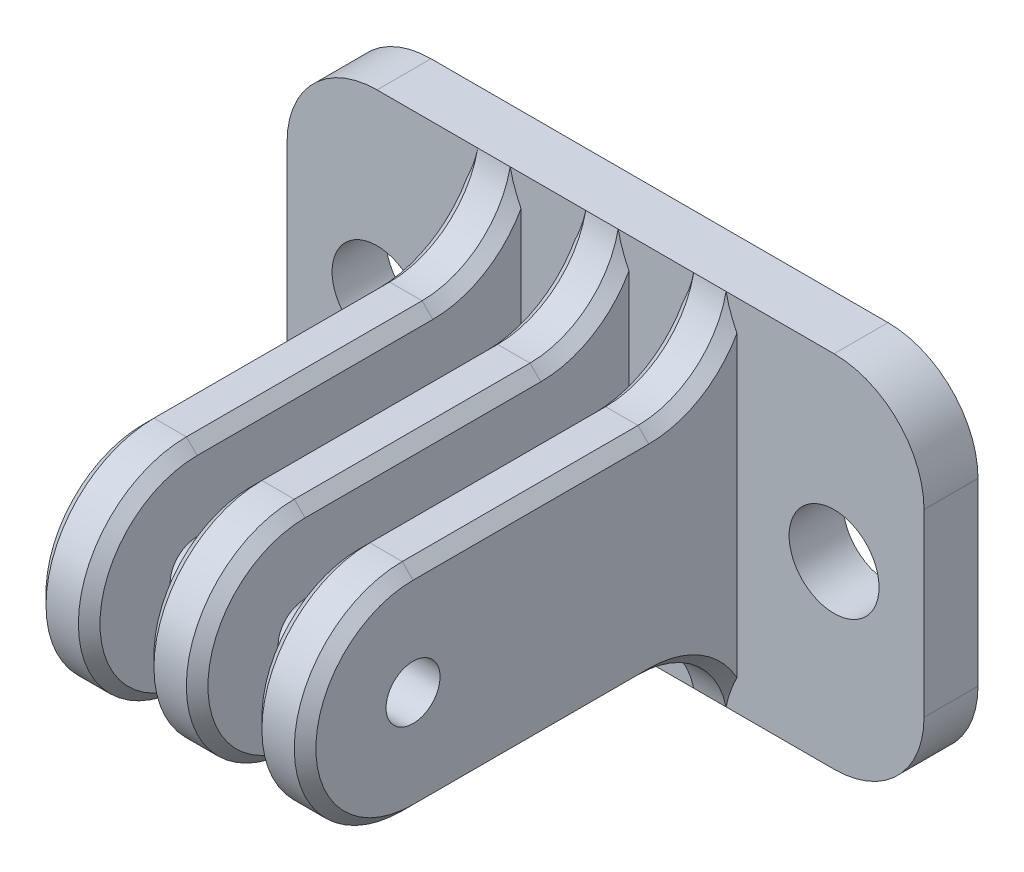
SolidWorks part; units mm, degrees
ref_plane "前视基准面" through (0, 0, 0) normal (0, 0, 1) x (1, 0, 0)
ref_plane "上视基准面" through (0, 0, 0) normal (0, 1, 0) x (1, 0, 0)
ref_plane "右视基准面" through (0, 0, 0) normal (1, 0, 0) x (0, 0, -1)
sketch "草图1" plane through (0, 0, 0) normal (0, 0, 1) x (1, 0, 0)
  line L1 (0, 0) -> (35.4, 0)
  line L2 (0, 0) -> (0, -20)
  line L3 (0, -20) -> (35.4, -20)
  line L4 (35.4, 0) -> (35.4, -20)
  circle A0 centre (5, -10) radius 2.5
  circle A1 centre (30.4, -10) radius 2.5
  point P10 (0, -10)
  dimension "D3" = 5
  dimension "D1" = 35.4
  dimension "D2" = 20
  dimension "D4" = 5
  dimension "D5" = 5
extrude "凸台-拉伸1" add sketch "草图1" along normal blind 3
sketch "草图3" plane through (0, 0, 0) normal (-1, 0, 0) x (0, 0, 1)
  line L0 (3, 0) -> (3, -20) construction
  line L1 (3, -4) -> (21, -4)
  line L2 (3, -4) -> (3, -16)
  line L3 (3, -16) -> (21, -16)
  line L4 (0, 0) -> (0, -20) construction
  arc A0 (21, -4) -> (21, -16) centre (21, -10) cw
  circle A1 centre (21, -10) radius 1.5
  point P8 (3, -10)
  point P11 (0, -10)
  dimension "D3" = 3
  dimension "D1" = 12
  dimension "D2" = 18
extrude "凸台-拉伸2" add sketch "草图3" against normal blind 3 from offset 10 offset against normal yes
pattern_linear "阵列(线性)1" count 3 spacing 6 along (1, 0, 0) of "凸台-拉伸2"
fillet "圆角1" radius 5 10 edges at (11.5, -16, 3) (17.5, -16, 3) (23.5, -16, 3) (11.5, -4, 3) (17.5, -4, 3) (23.5, -4, 3) (35.4, -20, 1.5) (35.4, 0, 1.5) (0, 0, 1.5) (0, -20, 1.5)
chamfer "倒角1" distance 0.6 angle 45 30 edges at (22, -17.127, 4.7367) (22, -2.873, 4.7367) (22, -16, 14.4495) (22, -4, 14.4495) (22, -10, 27) (16, -17.127, 4.7367) (16, -2.873, 4.7367) (16, -16, 14.4495) (16, -4, 14.4495) (16, -10, 27) (10, -17.127, 4.7367) (10, -2.873, 4.7367) (10, -16, 14.4495) (10, -4, 14.4495) (10, -10, 27) (25, -17.127, 4.7367) (25, -2.873, 4.7367) (25, -16, 14.4495) (25, -4, 14.4495) (25, -10, 27) (19, -17.127, 4.7367) (19, -2.873, 4.7367) (19, -16, 14.4495) (19, -4, 14.4495) (19, -10, 27) (13, -17.127, 4.7367) (13, -2.873, 4.7367) (13, -16, 14.4495) (13, -4, 14.4495) (13, -10, 27)
